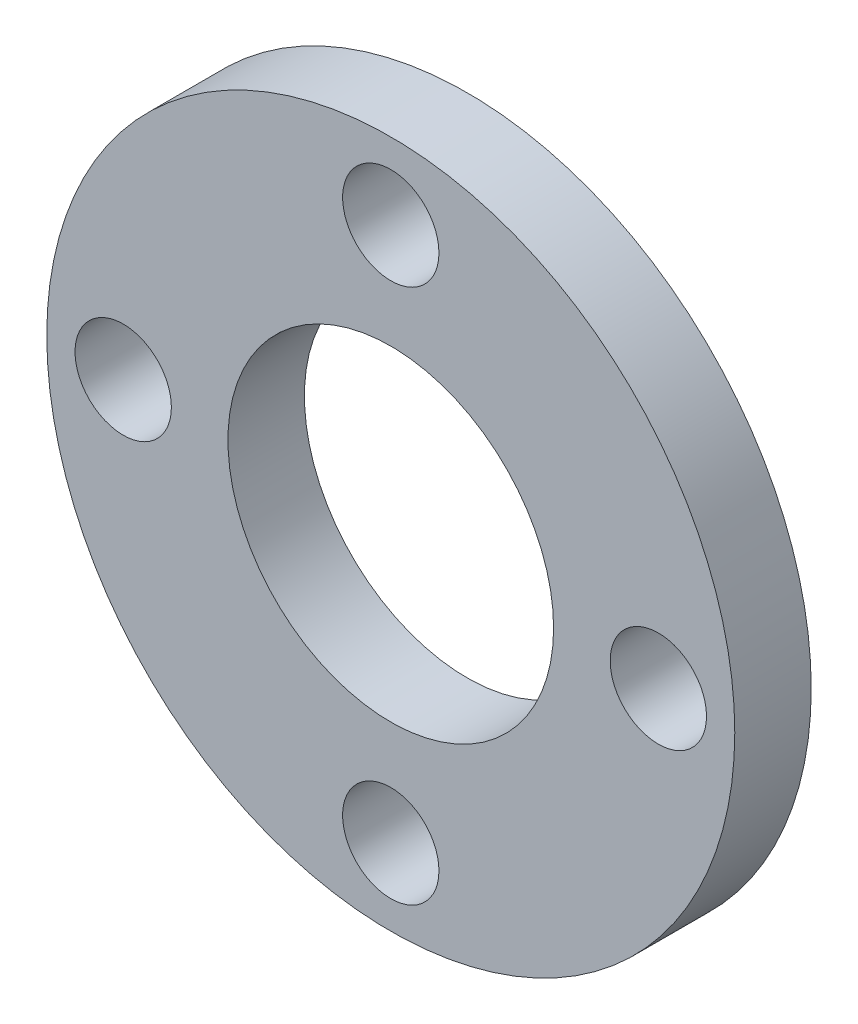
SolidWorks part; units mm, degrees
ref_plane "Płaszczyzna przednia" through (0, 0, 0) normal (0, 0, 1) x (1, 0, 0)
ref_plane "Płaszczyzna górna" through (0, 0, 0) normal (0, 1, 0) x (1, 0, 0)
ref_plane "Płaszczyzna prawa" through (0, 0, 0) normal (1, 0, 0) x (0, 0, -1)
sketch "Szkic1" plane through (0, 0, 0) normal (0, 0, 1) x (1, 0, 0)
  circle A0 centre (0, 0) radius 45
  circle A1 centre (0, 0) radius 35 construction
  circle A2 centre (0, 35) radius 6.3
  circle A3 centre (35, 0) radius 6.3
  circle A4 centre (0, -35) radius 6.3
  circle A5 centre (-35, 0) radius 6.3
  circle A6 centre (0, 0) radius 21.3
  dimension "D1" = 90
  dimension "D2" = 70
  dimension "D3" = 12.6
  dimension "D6" = 42.6
extrude "Dodanie-wyciągnięcie3" add sketch "Szkic1" along normal blind 10 contours A0 A5 A1 A2 A3 A4 | A5 A1 A4 A3 A2 A6 region at (-43.7272, 0, 0)
